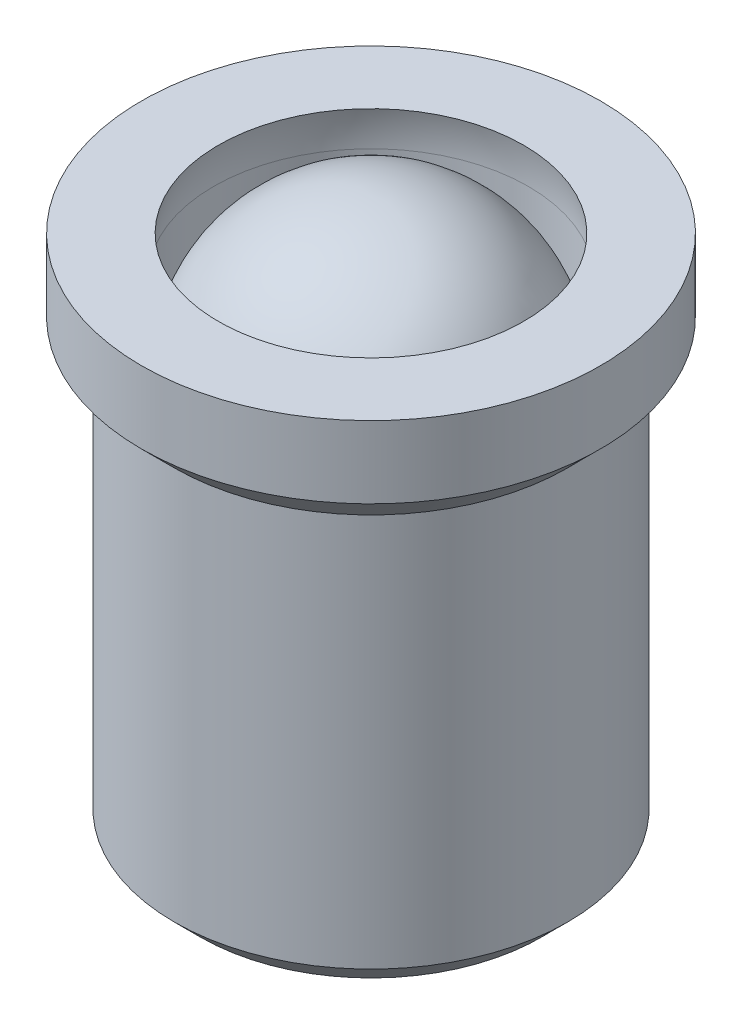
SolidWorks part; units mm, degrees
ref_plane "Front" through (0, 0, 0) normal (0, 0, 1) x (1, 0, 0)
ref_plane "Top" through (0, 0, 0) normal (0, 1, 0) x (1, 0, 0)
ref_plane "Right" through (0, 0, 0) normal (1, 0, 0) x (0, 0, -1)
sketch "草图1" plane through (0, 0, 0) normal (1, 0, 0) x (0, 0, -1)
  line L0 (0.3, 0) -> (1.5, 0)
  line L1 (1.5, 0) -> (1.5, 3.2)
  line L2 (1.5, 3.2) -> (1.75, 3.2)
  line L3 (1.75, 3.2) -> (1.75, 4)
  line L4 (1.75, 4) -> (1.1644, 4)
  line L6 (1.2, 0.3) -> (0.3, 0.3)
  line L8 (0, 0) -> (0, 5.4955) construction
  line L11 (0, 4.9) -> (-0.7192, 5.5273) construction
  line L19 (1.2, 3.71) -> (1.2, 0.3)
  line L20 (1.2, 0.29) -> (0.01, 0.29) construction
  line L21 (1.19, 0.3) -> (0, 0.3) construction
  line L22 (0.3, 0.3) -> (0.3, 0)
  line L23 (1.2, 3.71) -> (1.2, 0.29) construction
  line L24 (1.19, 3.71) -> (1.19, 0.3) construction
  line L25 (0.01, 0.01) -> (1.49, 0.01) construction
  line L26 (0.01, 0.29) -> (0.01, 0.01) construction
  line L27 (1.49, 0.01) -> (1.49, 3.21) construction
  line L28 (1.49, 3.21) -> (1.74, 3.21) construction
  line L29 (1.74, 3.21) -> (1.74, 3.99) construction
  line L30 (1.74, 3.99) -> (1.1669, 3.99) construction
  line L31 (1.75, 4) -> (1.1541, 4) construction
  line L33 (0, 0) -> (1.5, 0) construction
  line L34 (0, 0.3) -> (0, 0) construction
  arc A0 (0, 2.52) -> (0, 4.9) centre (0, 3.71) ccw construction
  arc A1 (1.2, 3.71) -> (1.1644, 4) centre (0, 3.71) ccw
  arc A2 (1.2, 3.71) -> (1.1669, 3.99) centre (0, 3.71) ccw construction
  arc A3 (1.19, 3.71) -> (1.1541, 4) centre (0, 3.71) ccw construction
  dimension "D6" = 2.38
  dimension "D1" = 1.5
  dimension "D2" = 4
  dimension "D3" = 0.8
  dimension "D4" = 0.9
  dimension "D5" = 1.75
  dimension "D7" = 0.01
  dimension "D8" = 0.3
  dimension "D9" = 0.3
  dimension "D10" = 0.3
revolve "旋转1" add sketch "草图1" angle 360 about L8
chamfer "倒角1" distance 0.2 angle 45 1 edges at (0, 0, -1.5)
sketch "草图2" plane through (0, 0, 0) normal (1, 0, 0) x (0, 0, -1)
  line L2 (0, 5.5329) -> (0, 0) construction
  line L3 (0, 4.25) -> (1.0891, 5.0223) construction
  line L4 (1.75, 4) -> (-1.75, 4) construction
  line L5 (0, 4.25) -> (0, 1.87)
  arc A1 (0, 1.87) -> (0, 4.25) centre (0, 3.06) ccw
  dimension "D1" = 2.38
  dimension "D2" = 0.25
revolve "旋转2" add sketch "草图2" angle 360 about L2
chamfer "倒角2" distance 0.25 angle 45 1 edges at (0, 3.2, -1.75)
